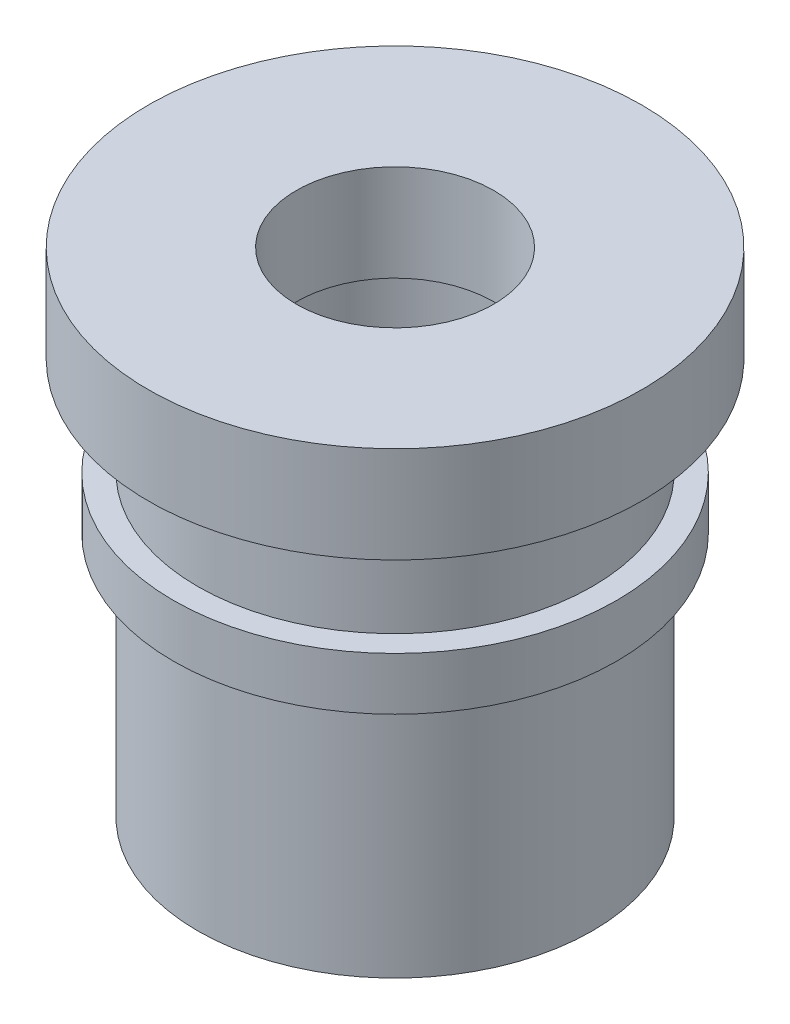
SolidWorks part; units mm, degrees
material "Rubber"
ref_plane "Front Plane" through (0, 0, 0) normal (0, 0, 1) x (1, 0, 0)
ref_plane "Top Plane" through (0, 0, 0) normal (0, 1, 0) x (1, 0, 0)
ref_plane "Right Plane" through (0, 0, 0) normal (1, 0, 0) x (0, 0, -1)
sketch "Sketch1" plane through (0, 0, 0) normal (0, 0, 1) x (1, 0, 0)
  line L0 (0, 0) -> (0, 39.1546) construction
  line L1 (3.9688, -2.1195) -> (3.9688, 49997.8805) construction
  line L2 (1.5875, 7.9375) -> (3.9688, 7.9375)
  line L3 (3.9688, 7.9375) -> (3.9688, 6.3865)
  line L4 (3.9688, 6.3865) -> (3.175, 6.3865)
  line L5 (3.175, 6.3865) -> (3.175, 4.799)
  line L6 (3.175, 4.799) -> (3.5642, 4.799)
  line L7 (3.5642, 4.799) -> (3.5642, 3.9518)
  line L8 (3.5642, 3.9518) -> (3.175, 3.9518)
  line L9 (3.175, 3.9518) -> (3.175, 0)
  line L10 (3.175, 0) -> (1.8978, 0)
  line L11 (1.8978, 0) -> (1.8978, 6.3865)
  line L12 (1.8978, 6.3865) -> (1.5875, 6.3865)
  line L13 (1.5875, 6.3865) -> (1.5875, 7.9375)
  line L14 (-1.5875, 6.3865) -> (-1.5875, 7.9375) construction
  line L15 (-1.8978, 6.3865) -> (-1.5875, 6.3865) construction
  line L16 (-1.8978, 0) -> (-1.8978, 6.3865) construction
  line L17 (-3.175, 0) -> (-1.8978, 0) construction
  line L18 (-3.175, 3.9518) -> (-3.175, 0) construction
  line L19 (-3.5642, 3.9518) -> (-3.175, 3.9518) construction
  line L20 (-3.5642, 4.799) -> (-3.5642, 3.9518) construction
  line L21 (-3.175, 4.799) -> (-3.5642, 4.799) construction
  line L22 (-3.175, 6.3865) -> (-3.175, 4.799) construction
  line L23 (-3.9688, 6.3865) -> (-3.175, 6.3865) construction
  line L24 (-3.9688, 7.9375) -> (-3.9688, 6.3865) construction
  line L25 (-1.5875, 7.9375) -> (-3.9688, 7.9375) construction
  dimension "D1" = 3.175
  dimension "D2" = 7.9375
  dimension "D3" = 7.9375
  dimension "D4" = 6.35
  dimension "D5" = 1.5875
revolve "Revolve1" add sketch "Sketch1" angle 360 about L0
ref_axis "Axis1" through (0, 7.9375, 0) along (0, -1, 0)
